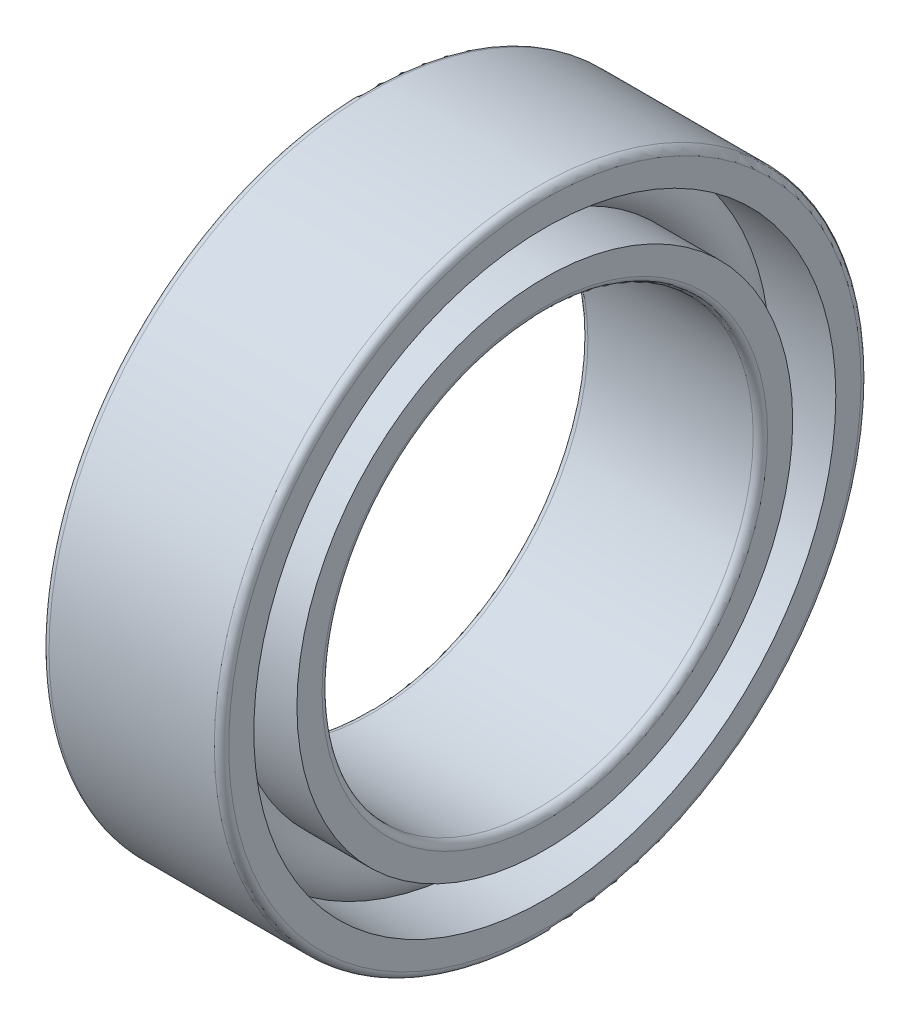
SolidWorks part; units mm, degrees
ref_plane "Plane1" through (0, 0, 0) normal (0, 0, 1) x (1, 0, 0)
ref_plane "Plane2" through (0, 0, 0) normal (0, 1, 0) x (1, 0, 0)
ref_plane "Plane3" through (0, 0, 0) normal (1, 0, 0) x (0, 0, -1)
other "Configuration Table"
sketch "Clipboard" plane through (0, 0, 0) normal (0, 0, 1) x (1, 0, 0)
  line L0 (-10, 0) -> (10, 0) construction
  line L1 (0, 0) -> (22.3471, -0.7804)
  line L2 (0, 0) -> (7.4954, 0.2617)
  line L3 (0, 0) -> (22.3471, -0.7804)
  line L4 (0, 0) -> (-22.3573, -0.3902)
  dimension "BallCLRad" = 7.5
sketch "CagSpiSke" plane through (0, 0, 0) normal (0, 0, 1) x (1, 0, 0)
  line L0 (0.09, 7.35) -> (0.09, 7.65)
  line L1 (0.09, 7.65) -> (-0.09, 7.65)
  line L2 (-0.09, 7.65) -> (-0.09, 7.35)
  line L3 (-0.09, 7.35) -> (0.09, 7.35)
  line L4 (-20.6375, 0) -> (20.6375, 0) construction
  line L5 (0, 0) -> (0, 23.7692) construction
  dimension "OD" = 15.3
  dimension "ID" = 14.7
revolve "CageSpine" add sketch "CagSpiSke" angle 0.001 about L4 reverse direction yes
ref_axis "Axis1" through (-50, 0, 0) along (1, 0, 0)
sketch "CagBalSke" plane through (0, 0, 0) normal (0, 0, 1) x (1, 0, 0)
  line L0 (-0.99, 7.5) -> (0.99, 7.5)
  line L1 (-1.905, 7.5) -> (1.905, 7.5) construction
  line L2 (-10, 0) -> (10, 0) construction
  line L3 (0, 0) -> (0, 24) construction
  arc A0 (0.99, 7.5) -> (-0.99, 7.5) centre (0, 7.5) cw
  dimension "BallCLRad" = 7.5
revolve "CageBall" [suppressed] add sketch "CagBalSke" angle 360 about L1 reverse direction yes
pattern_circular "CageBalls" [suppressed] count 2 every 180 about axis through (-50, 0, 0) along (1, 0, 0)
sketch "CagTrmODSke" plane through (0, 0, 0) normal (0, 0, 1) x (1, 0, 0)
  line L0 (0.991, 7.65) -> (0.991, 8.491)
  line L1 (0.991, 8.491) -> (-0.991, 8.491)
  line L2 (-0.991, 8.491) -> (-0.991, 7.65)
  line L3 (-0.991, 7.65) -> (0.991, 7.65)
  line L4 (-20.6375, 0) -> (20.6375, 0) construction
  line L5 (0, 0) -> (0, 25) construction
  dimension "Width" = 1.982
  dimension "ID" = 15.3
  dimension "OD" = 16.982
revolve "CageTrimOD" [suppressed] cut sketch "CagTrmODSke" angle 360 about L4 reverse direction yes
sketch "CagTrmIDSke" plane through (0, 0, 0) normal (0, 0, 1) x (1, 0, 0)
  line L0 (0.991, 6.511) -> (0.991, 7.35)
  line L1 (0.991, 7.35) -> (-0.991, 7.35)
  line L2 (-0.991, 7.35) -> (-0.991, 6.511)
  line L3 (-0.991, 6.511) -> (0.991, 6.511)
  line L4 (-20.6375, 0) -> (20.6375, 0) construction
  line L5 (0, 0) -> (0, 25) construction
  dimension "Width" = 1.982
  dimension "ID" = 13.022
  dimension "OD" = 14.7
revolve "CageTrimID" [suppressed] cut sketch "CagTrmIDSke" angle 360 about L4 reverse direction yes
sketch "BalSimSke" plane through (0, 0, 0) normal (0, 0, 1) x (1, 0, 0)
  line L0 (-10, 0) -> (10, 0) construction
  line L1 (-10, 7.5) -> (10, 7.5) construction
  line L2 (0, 0) -> (0, 23) construction
  circle A0 centre (0, 7.5) radius 0.9
  dimension "BallCLRad" = 7.5
  dimension "Ball_diameter" = 1.8
revolve "BallsSimplified" add sketch "BalSimSke" angle 360 about L0
sketch "BalDetSke" plane through (0, 0, 0) normal (0, 0, 1) x (1, 0, 0)
  line L0 (-0.9, 7.5) -> (0.9, 7.5)
  line L1 (-1.905, 7.5) -> (1.905, 7.5) construction
  line L2 (0, 0) -> (0, 25) construction
  arc A0 (0.9, 7.5) -> (-0.9, 7.5) centre (0, 7.5) cw
  dimension "BallCLRad" = 7.5
  dimension "Ball_diameter" = 1.8
revolve "BallDetailed" [suppressed] add sketch "BalDetSke" angle 360 about L1 reverse direction yes
sketch "InnRacSke" plane through (0, 0, 0) normal (0, 0, 1) x (1, 0, 0)
  line L0 (-0.6369, 6.9) -> (-2.5, 6.9)
  line L1 (-2.5, 6.9) -> (-2.5, 6.2)
  line L2 (-2.3, 6) -> (2.3, 6)
  line L3 (2.5, 6.2) -> (2.5, 6.9)
  line L4 (2.5, 6.9) -> (0.6369, 6.9)
  line L5 (-20.6375, 0) -> (20.6375, 0) construction
  line L6 (0, 0) -> (0, 30) construction
  arc A0 (-2.5, 6.2) -> (-2.3, 6) centre (-2.3, 6.2) ccw
  arc A1 (2.3, 6) -> (2.5, 6.2) centre (2.3, 6.2) ccw
  arc A2 (0.6369, 6.9) -> (-0.6369, 6.9) centre (0, 7.5) cw
  dimension "BallCLRad" = 7.5
  dimension "Fillet_radius" = 0.2
  dimension "Ball_diameter" = 1.75
  dimension "ID" = 12
  dimension "OD" = 13.8
  dimension "Width" = 5
revolve "InnerRace" add sketch "InnRacSke" angle 360 about L5 reverse direction yes
sketch "OutRacSke" plane through (0, 0, 0) normal (0, 0, 1) x (1, 0, 0)
  line L0 (-0.6369, 8.1) -> (-2.5, 8.1)
  line L1 (-2.5, 8.1) -> (-2.5, 8.8)
  line L2 (-2.3, 9) -> (2.3, 9)
  line L3 (2.5, 8.8) -> (2.5, 8.1)
  line L4 (2.5, 8.1) -> (0.6369, 8.1)
  line L5 (-20.6375, 0) -> (20.6375, 0) construction
  line L6 (0, 0) -> (0, 30) construction
  arc A0 (-2.5, 8.8) -> (-2.3, 9) centre (-2.3, 8.8) cw
  arc A1 (2.3, 9) -> (2.5, 8.8) centre (2.3, 8.8) cw
  arc A2 (0.6369, 8.1) -> (-0.6369, 8.1) centre (0, 7.5) ccw
  dimension "BallCLRad" = 7.5
  dimension "Fillet_radius" = 0.2
  dimension "Ball_diameter" = 1.75
  dimension "Width" = 5
revolve "OuterRace" add sketch "OutRacSke" angle 360 about L5 reverse direction yes
pattern_circular "BallsDetailed" [suppressed] count 2 every 180 about axis through (-50, 0, 0) along (1, 0, 0)
scale "Scale1" scale about centroid uniform scaling yes scale factor 0.317565
equation "\"BallCLRad@Clipboard\" = ( \"OD@OutRacSke\" + \"ID@InnRacSke\" ) / 4"
equation "\"BallCLRad@BalSimSke\" = \"BallCLRad@Clipboard\""
equation "\"BallCLRad@BalDetSke\" = \"BallCLRad@Clipboard\""
equation "\"BallCLRad@InnRacSke\" = \"BallCLRad@Clipboard\""
equation "\"BallCLRad@OutRacSke\" = \"BallCLRad@Clipboard\""
equation "\"Ball_diameter@InnRacSke\" = \"Ball_diameter@BalDetSke\" - 0.05"
equation "\"Ball_diameter@OutRacSke\" = \"Ball_diameter@BalDetSke\" - 0.05"
equation "\"Ball_diameter@BalSimSke\" = \"Ball_diameter@BalDetSke\""
equation "\"Width@OutRacSke\" = \"Width@InnRacSke\""
equation "\"Fillet_radius@OutRacSke\" = \"Fillet_radius@InnRacSke\""
equation "\"Max_count@Clipboard\" = int( 3.14159265 / atn(( \"Ball_diameter@BalDetSke\" / 2) / sqr( \"BallCLRad@Clipboard\"  *  \"BallCLRad@Clipboard\" - ( \"Ball_diameter@BalDetSke\" / 2) *  ( \"Ball_diameter@BalDetSke\" / 2))))"
equation "\"Max_count@Clipboard\" = ((sgn( \"Max_count@Clipboard\" - \"Count@Clipboard\" )-1)*( \"Max_count@Clipboard\" - \"Count@Clipboard\" ))/-2+ \"Count@Clipboard\""
equation "\"Count@BallsDetailed\" = int( \"Show_count@Clipboard\" ) "
equation "\"Count@BallsDetailed\" = ((sgn( \"Count@BallsDetailed\" - \"Max_count@Clipboard\" )-1)*( \"Count@BallsDetailed\" - \"Max_count@Clipboard\" ))/-2+ \"Max_count@Clipboard\""
equation "\"Count@BallsDetailed\" = ((sgn( \"Count@BallsDetailed\" - \"Min_count@Clipboard\" )+1)*( \"Count@BallsDetailed\" - \"Min_count@Clipboard\"))/2 +\"Min_count@Clipboard\""
equation "\"Angle@BallsDetailed\" = 360.0 / \"Max_count@Clipboard\""
equation "\"BallCLRad@CagBalSke\" = \"BallCLRad@Clipboard\""
equation "\"Count@CageBalls\" = \"Count@BallsDetailed\""
equation "\"Angle@CageBalls\" = \"Angle@BallsDetailed\""
equation "\"Angle@CageSpine\" =  \"Angle@CageBalls\" * ( \"Count@CageBalls\" -1 + int( \"Count@CageBalls\" / \"Max_count@Clipboard\" ) )  + 0.001 -  int( \"Count@CageBalls\" / \"Max_count@Clipboard\" ) * 0.001"
equation "\"Angle@CageSpine\" =  \"Angle@CageSpine\" * int( \"Min_count@Clipboard\" / 2) + int(1 / \"Min_count@Clipboard\")  * 0.001"
equation "\"CageWallOD@CagBalSke\" =  \"Ball_diameter@BalDetSke\" * 1.1"
equation "\"Thickness@CagSpiSke\" =  \"Ball_diameter@BalDetSke\" * 0.1"
equation "\"OD@CagTrmODSke\" = \"BallCLRad@Clipboard\" * 2 + \"CageWallOD@CagBalSke\" + 0.002"
equation "\"ID@CagTrmODSke\" = \"BallCLRad@Clipboard\" * 2 + \"Ball_diameter@BalDetSke\" / 6"
equation "\"OD@CagTrmIDSke\" = \"BallCLRad@Clipboard\" * 2 - \"Ball_diameter@BalDetSke\" / 6"
equation "\"ID@CagTrmIDSke\" = \"BallCLRad@Clipboard\" * 2 - \"CageWallOD@CagBalSke\" + 0.002"
equation "\"OD@CagSpiSke\" = \"ID@CagTrmODSke\""
equation "\"ID@CagSpiSke\" = \"OD@CagTrmIDSke\""
equation "\"Width@CagTrmODSke\" = \"CageWallOD@CagBalSke\" + 0.002"
equation "\"Width@CagTrmIDSke\" = \"CageWallOD@CagBalSke\" + 0.002"
